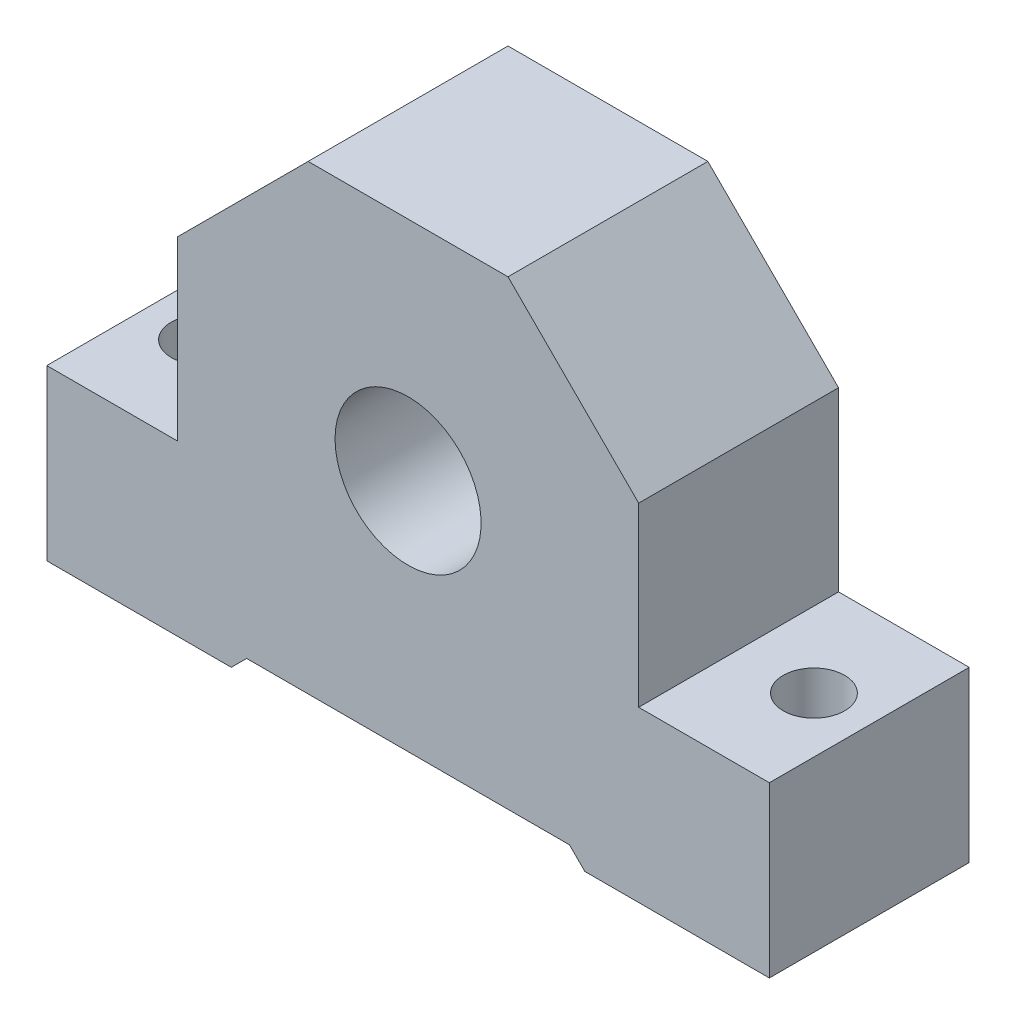
SolidWorks part; units mm, degrees
ref_plane "Płaszczyzna przednia" through (0, 0, 0) normal (0, 0, 1) x (1, 0, 0)
ref_plane "Płaszczyzna górna" through (0, 0, 0) normal (0, 1, 0) x (1, 0, 0)
ref_plane "Płaszczyzna prawa" through (0, 0, 0) normal (1, 0, 0) x (0, 0, -1)
sketch "Szkic1" plane through (0, 0, 0) normal (0, 0, 1) x (1, 0, 0)
  line L0 (-47, 11) -> (-30, 11)
  line L2 (47, -11) -> (47, 11)
  line L4 (-47, -11) -> (-47, 11)
  line L5 (47, -11) -> (-47, 11) construction
  line L6 (47, 11) -> (-47, -11) construction
  line L7 (-30, 11) -> (-30, 34)
  line L8 (-30, 34) -> (-13, 51)
  line L9 (-13, 51) -> (13, 51)
  line L10 (13, 51) -> (30, 34)
  line L11 (30, 34) -> (30, 11)
  line L12 (30, 11) -> (47, 11)
  line L13 (-47, -11) -> (-23, -11)
  line L14 (-23, -11) -> (-21, -9)
  line L15 (-21, -9) -> (21, -9)
  line L16 (21, -9) -> (23, -11)
  line L17 (23, -11) -> (47, -11)
  point P0 (0, 0)
  point P18 (35, -11)
  dimension "D1" = 94
  dimension "D2" = 26
  dimension "D3" = 26
  dimension "D4" = 135
  dimension "D5" = 135
  dimension "D6" = 17
  dimension "D7" = 26
  dimension "D8" = 2
  dimension "D9" = 135
  dimension "D10" = 135
  dimension "D11" = 62
  dimension "D12" = 22
  dimension "D13" = 60
  dimension "D14" = 17
  dimension "D15" = 17
extrude "Dodanie-wyciągnięcie1" add sketch "Szkic1" along normal blind 26
sketch "Szkic3" plane through (0, 0, 0) normal (0, 0, -1) x (-1, 0, 0)
  line L0 (-13, 51) -> (13, 51) construction
  circle A0 centre (0, 21.5) radius 9.5
  dimension "D1" = 29.5
extrude "Wytnij-wyciągnięcie1" cut sketch "Szkic3" against normal blind 26
sketch "Szkic4" plane through (0, 11, 0) normal (0, 1, 0) x (1, 0, 0)
  line L0 (47, -26) -> (47, 0) construction
  line L1 (47, 0) -> (30, 0) construction
  line L2 (-47, -26) -> (-47, 0) construction
  line L3 (-30, 0) -> (-47, 0) construction
  circle A0 centre (39.8, -13) radius 4
  circle A1 centre (-39.8, -13) radius 4
  point P10 (-47, -13)
  dimension "D1" = 7.2
  dimension "D3" = 7.2
  dimension "D2" = 13
  dimension "D4" = 13
extrude "Wytnij-wyciągnięcie2" cut sketch "Szkic4" against normal blind 22
